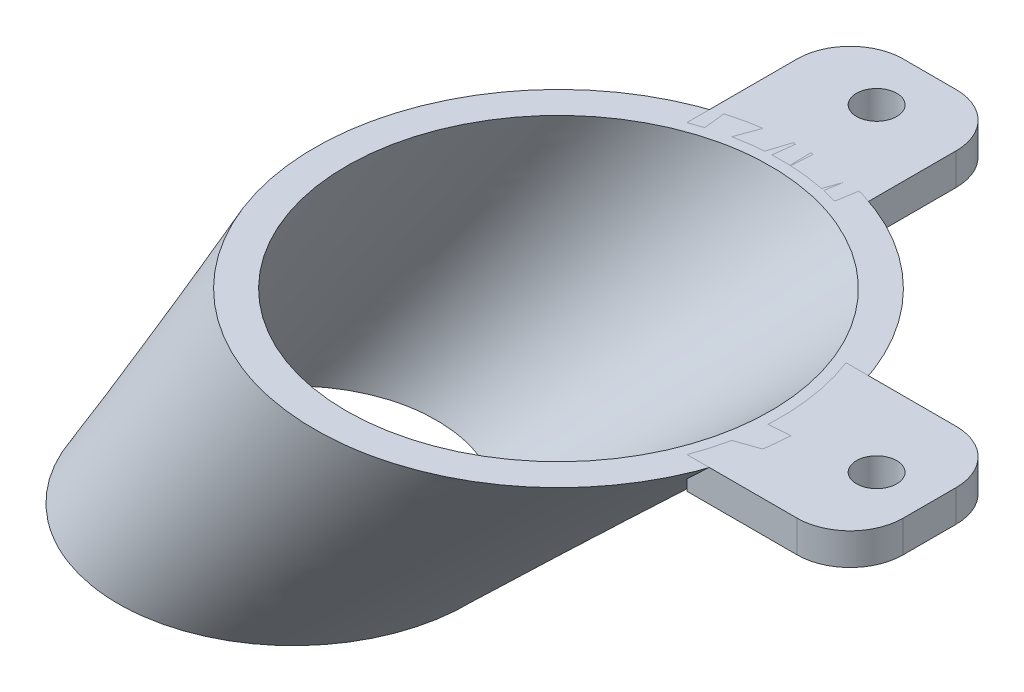
SolidWorks part; units mm, degrees
ref_plane "Front Plane" through (0, 0, 0) normal (0, 0, 1) x (1, 0, 0)
ref_plane "Top Plane" through (0, 0, 0) normal (0, 1, 0) x (1, 0, 0)
ref_plane "Right Plane" through (0, 0, 0) normal (1, 0, 0) x (0, 0, -1)
sketch "Sketch1" plane through (0, 0, 0) normal (0, 1, 0) x (1, 0, 0)
  line L0 (0, 0) -> (-47.9811, 0) construction
  circle A0 centre (0, 0) radius 23
  dimension "D1" = 46
ref_plane "Plane1" through (0, -30, 0) normal (0, -1, 0) x (-1, 0, 0)
sketch "Sketch9" plane through (0, -30, 0) normal (0, -1, 0) x (-1, 0, 0)
  circle A0 centre (25, 0) radius 16.5
  dimension "D1" = 33
  dimension "D2" = 25
loft "Loft1" add profiles "Sketch9", "Sketch1" connector at (-20.6661, -30, -15.9207) connector at (1.0526, 0, -22.9759)
sketch "Sketch13" plane through (0, 0, 0) normal (0, 1, 0) x (1, 0, 0)
  circle A0 centre (0, 0) radius 20
  dimension "D1" = 40
sketch "Sketch14" plane through (0, -30, 0) normal (0, -1, 0) x (1, 0, 0)
  circle A0 centre (-25, 0) radius 13.5
  dimension "D1" = 27
loft "Cut-Loft1" cut profiles "Sketch13", "Sketch14" connector at (-1.7195, 0, 19.9259) connector at (-25.3909, -30, 13.4943)
sketch "Sketch16" plane through (0, 0, 0) normal (0, 1, 0) x (1, 0, 0)
  line L0 (-16.5091, 0) -> (16.5091, 0) construction
  line L1 (-2.5, 35) -> (2.5, 35)
  line L2 (-7.5, 30) -> (-7.5, 19.615)
  line L4 (7.5, 30) -> (7.5, 19.615)
  line L5 (35, 2.5) -> (35, -2.5)
  line L6 (30, -7.5) -> (19.615, -7.5)
  line L7 (30, 7.5) -> (19.615, 7.5)
  line L8 (0, 0) -> (7.5, 19.615) construction
  line L9 (0, 0) -> (19.615, -7.5) construction
  circle A0 centre (0, 0) radius 23 construction
  arc A1 (7.5, 19.615) -> (-7.5, 19.615) centre (0, 0) ccw
  arc A2 (2.5, 35) -> (7.5, 30) centre (2.5, 30) cw
  arc A3 (-2.5, 35) -> (-7.5, 30) centre (-2.5, 30) ccw
  arc A4 (35, 2.5) -> (30, 7.5) centre (30, 2.5) ccw
  arc A5 (35, -2.5) -> (30, -7.5) centre (30, -2.5) cw
  arc A6 (19.615, -7.5) -> (19.615, 7.5) centre (0, 0) ccw
  point P0 (0, 23)
  point P8 (0, 21)
  dimension "D2" = 42
  dimension "D4" = 5
  dimension "D5" = 2
  dimension "D1" = 14
  dimension "D3" = 15
  dimension "D6" = 90
extrude "Boss-Extrude1" add sketch "Sketch16" against normal blind 3 separate body
hole_wizard "#10-24 Tapped Hole1" positions "Sketch17" profile "Sketch18" tap size "#10-24" standard "ANSI Inch" end condition through all
sketch "Sketch17" plane through (0, 0, 0) normal (0, 1, 0) x (1, 0, 0)
  line L1 (2.5, 35) -> (-2.5, 35) construction
  line L2 (35, -2.5) -> (35, 2.5) construction
  point P0 (0, 30)
  point P9 (30, 0)
  dimension "D2" = 5
  dimension "D1" = 5
sketch "Sketch18" plane through (0, 0, -30) normal (1, 0, 0) x (0, 0, 1)
  line L0 (0, 0) -> (0, 30.0083)
  line L1 (0, 30.0083) -> (1.8986, 30.0083)
  line L2 (1.8986, 30.0083) -> (1.8986, 0)
  line L5 (1.8986, 0) -> (0, 0)
  line L11 (0, -6.35) -> (0, 107.95) construction
  dimension "Thru Tap Drill Dia." = 3.7973
  dimension "Thru Tap Drill Depth" = 30.0083
cosmetic thread "Hole Thread2" parameters "D2"=4.826
cosmetic thread "Hole Thread3" parameters "D2"=4.826
equation "\"D1@Sketch17\"=\"D2@Sketch17\""
